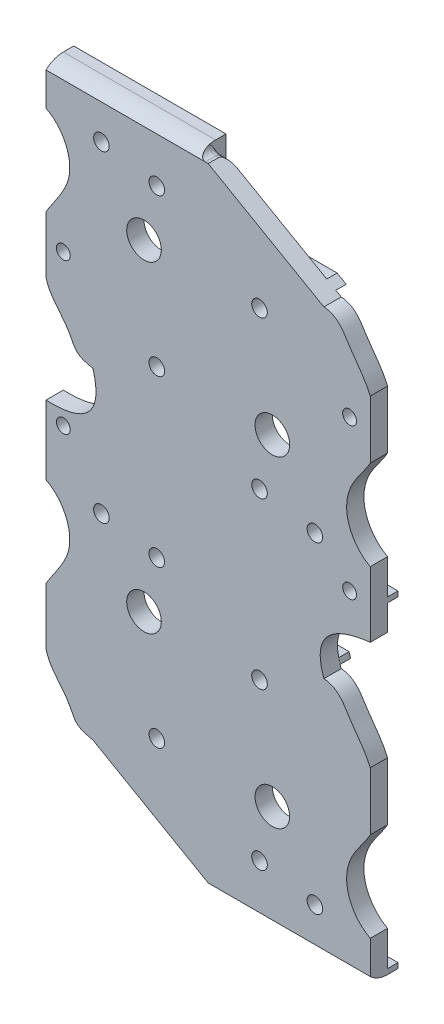
SolidWorks part; units mm, degrees
ref_plane "Front Plane" through (0, 0, 0) normal (0, 0, 1) x (1, 0, 0)
ref_plane "Top Plane" through (0, 0, 0) normal (0, 1, 0) x (1, 0, 0)
ref_plane "Right Plane" through (0, 0, 0) normal (1, 0, 0) x (0, 0, -1)
sketch "Sketch1" plane through (0, 0, 0) normal (0, 0, 1) x (1, 0, 0)
  line L0 (-19.7692, 94.7302) -> (-48.0392, 94.7302) construction
  line L1 (-46.8389, 110) -> (46.8389, 110)
  line L2 (-46.8389, 110) -> (-46.8389, -70)
  line L3 (-46.8389, -70) -> (46.8389, -70)
  line L4 (46.8389, 110) -> (46.8389, -70)
  line L5 (-46.8389, 27.4128) -> (-46.8389, 58.1094)
  line L6 (-46.8389, 100.4217) -> (-46.8597, 74.4838)
  line L7 (46.8389, 13.6344) -> (46.8389, -17.7446)
  line L8 (46.8389, 106.6344) -> (46.8389, 75.2554)
  line L9 (46.8389, 32.5783) -> (46.8597, 58.5162)
  line L10 (46.8389, -60.4217) -> (46.8597, -34.4838)
  line L11 (-46.8389, -65.5872) -> (-46.8389, -34.8906)
  line L12 (-46.8389, 7.4217) -> (-46.8597, -18.5162)
  line L13 (-33.2661, -50.893) -> (0, -70)
  line L14 (0, -70) -> (-46.8389, -70)
  line L15 (-46.8389, -34.8906) -> (-46.8389, -70)
  line L16 (33.4436, 90.8587) -> (0, 110)
  arc A0 (-42.3622, 81.2908) -> (-46.8389, 100.4217) centre (-53.2184, 88.8396) ccw construction
  arc A1 (-42.3622, 81.2908) -> (-46.8597, 74.4838) centre (98.8539, -16.903) ccw construction
  arc A2 (-44.9811, 54.2562) -> (-41.0297, 48.7592) centre (4.5296, 85.6771) ccw construction
  arc A3 (-38.5976, 44.9453) -> (-41.0297, 48.7592) centre (-56.5685, 36.1677) ccw construction
  arc A4 (-40.9236, 48.3818) -> (-37.2194, 45.4511) centre (-33.0423, 54.5369) ccw construction
  arc A5 (-38.5976, 44.9453) -> (-36.9529, 43.1656) centre (-34.8111, 46.7947) ccw construction
  arc A6 (-36.9529, 43.1656) -> (-29.4469, 41.75) centre (-29.4469, 62.3575) ccw construction
  circle A7 centre (-14.8389, 51.75) radius 2.25
  arc A8 (42.3622, 51.7092) -> (46.8389, 32.5783) centre (53.2184, 44.1604) ccw construction
  arc A9 (42.3622, 51.7092) -> (46.8597, 58.5162) centre (-98.8539, 149.903) ccw construction
  arc A10 (36.9529, 89.8344) -> (29.4469, 91.25) centre (29.4469, 70.6425) ccw construction
  circle A11 centre (-14.8389, 97) radius 2.25
  circle A12 centre (-30.8389, 100) radius 2.25
  circle A13 centre (14.8389, 81.25) radius 2.25
  circle A14 centre (14.8389, 36) radius 2.25
  circle A15 centre (30.8389, 33) radius 2.25
  circle A16 centre (-14.8389, -41.25) radius 2.25
  circle A17 centre (-14.8389, 4) radius 2.25
  circle A18 centre (-30.8389, 7) radius 2.25
  circle A19 centre (14.8389, -11.75) radius 2.25
  circle A20 centre (14.8389, -57) radius 2.25
  circle A21 centre (30.8389, -60) radius 2.25
  spline S0 degree 3 poles (-46.8389, 100.4217) (-42.2264, 98.1412) (-36.7036, 86.8939) (-44.5501, 78.531) (-46.8597, 74.4838) knots 0 0 0 0 0.513387 1 1 1 1
  spline S1 degree 3 poles (-46.8389, 58.1094) (-45.7586, 53.6552) (-40.8859, 50.4065) (-38.2385, 43.1366) (-34.7821, 42.4316) (-33.2661, 42.107) knots 0 0 0 0 0.587735 0.769686 1 1 1 1
  spline S2 degree 2 poles (-33.2661, 42.107) (-28.8924, 26.7095) (-46.8389, 27.4128) knots 0 0 0 1 1 1
  spline S3 degree 3 poles (46.8389, 32.5783) (42.9828, 34.6042) (38.9062, 41.1287) (41.1418, 51.3815) (45.2094, 55.5599) (46.8597, 58.5162) knots 0 0 0 0 0.434931 0.661678 1 1 1 1
  spline S4 degree 3 poles (46.8389, 75.2554) (45.396, 78.7223) (40.759, 83.9953) (37.5733, 90.552) (33.4436, 90.8587) knots 0 0 0 0 0.525455 1 1 1 1
  spline S7 degree 3 poles (-46.8389, -34.8906) (-45.7586, -39.3448) (-40.8859, -42.5935) (-38.2385, -49.8634) (-34.7821, -50.5684) (-33.2661, -50.893) knots 0 0 0 0 0.587735 0.769686 1 1 1 1
  spline S8 degree 3 poles (-46.8389, 7.4217) (-42.2264, 5.1412) (-36.7036, -6.1061) (-44.5501, -14.469) (-46.8597, -18.5162) knots 0 0 0 0 0.513387 1 1 1 1
  spline S9 degree 2 poles (33.4436, -2.1413) (28.4165, 11.5595) (46.8389, 13.6344) knots 0 0 0 1 1 1
  spline S10 degree 3 poles (46.8389, -17.7446) (45.396, -14.2777) (40.759, -9.0047) (37.5733, -2.448) (33.4436, -2.1413) knots 0 0 0 0 0.525455 1 1 1 1
  spline S11 degree 3 poles (46.8389, -60.4217) (42.9828, -58.3958) (38.9062, -51.8713) (41.1418, -41.6185) (45.2094, -37.4401) (46.8597, -34.4838) knots 0 0 0 0 0.434931 0.661678 1 1 1 1
  dimension "D1" = 4.5
  dimension "D2" = 4.5
  dimension "D3" = 4.5
  dimension "D4" = 4.5
  dimension "D6" = 44.75
  dimension "D5" = 2
extrude "Boss-Extrude1" add sketch "Sketch1" along normal blind 5 contours L4 S11 S10 S9 S3 S4 L1 L2 S0 S1 S2 S8 S7 L3 region at (-0.0047, 20.0102, 0)
sketch "Sketch2" plane through (0, 0, 0) normal (0, 0, -1) x (-1, 0, 0)
  line L1 (46.8389, 27.4128) -> (46.8389, 7.4217) construction
  line L3 (2.8389, 19) -> (46.8389, 19)
  line L4 (46.8389, 19) -> (46.8389, 17.5)
  line L5 (4.8389, 17) -> (46.8389, 17) construction
  line L6 (46.8389, 17.5) -> (4.3389, 17.5)
  line L7 (4.3389, 17.5) -> (4.3389, -51.75)
  line L8 (4.3389, -51.75) -> (31.774, -51.75)
  line L9 (33.2661, -50.893) -> (0, -70) construction
  line L10 (31.774, -51.75) -> (29.1624, -53.25)
  line L11 (29.1624, -53.25) -> (2.8389, -53.25)
  line L12 (2.8389, -53.25) -> (2.8389, 19)
  line L14 (4.8389, 17) -> (4.8389, -51.25) construction
  line L15 (-33.1375, -1.25) -> (-32.7243, 0.25)
  line L16 (4.8389, -51.25) -> (29.4469, -51.25) construction
  line L17 (46.8389, 110.5) -> (4.3389, 110.5)
  line L18 (46.8389, 112) -> (46.8389, 110.5)
  line L19 (2.8389, 112) -> (46.8389, 112)
  line L20 (2.8389, 39.75) -> (2.8389, 112)
  line L21 (4.3389, 110.5) -> (4.3389, 41.25)
  line L22 (32.7098, 39.75) -> (2.8389, 39.75)
  line L23 (4.3389, 41.25) -> (33.0368, 41.25)
  line L25 (-46.8389, -60.4217) -> (-46.8389, -70) construction
  line L26 (33.0368, 41.25) -> (32.7098, 39.75)
  line L27 (-2.8389, 21) -> (-46.8389, 21)
  line L28 (4.8389, 41.75) -> (29.4469, 41.75) construction
  line L29 (46.8389, 110) -> (0, 110) construction
  line L30 (4.8389, 110) -> (4.8389, 41.75) construction
  line L31 (46.8389, 110) -> (46.8389, 100.4217) construction
  line L32 (-46.8389, 22.5) -> (-4.3389, 22.5)
  line L33 (-46.8389, 21) -> (-46.8389, 22.5)
  line L34 (-2.8389, 93.25) -> (-2.8389, 21)
  line L35 (-4.3389, 22.5) -> (-4.3389, 91.75)
  line L36 (-29.2656, 93.25) -> (-2.8389, 93.25)
  line L37 (-4.3389, 91.75) -> (-31.8864, 91.75)
  line L39 (-4.8389, 23) -> (-46.8389, 23) construction
  line L40 (-33.4436, 90.8587) -> (0, 110) construction
  line L41 (-29.2656, 93.25) -> (-31.8864, 91.75)
  line L42 (-4.8389, 91.25) -> (-29.4469, 91.25) construction
  line L43 (-4.8389, 23) -> (-4.8389, 91.25) construction
  line L44 (-46.8389, -70.5) -> (-4.3389, -70.5)
  line L45 (-4.3389, -70.5) -> (-4.3389, -1.25)
  line L46 (-4.3389, -1.25) -> (-33.1375, -1.25)
  line L47 (-32.7243, 0.25) -> (-2.8389, 0.25)
  line L48 (-2.8389, 0.25) -> (-2.8389, -72)
  line L49 (-2.8389, -72) -> (-46.8389, -72)
  line L50 (-46.8389, -72) -> (-46.8389, -70.5)
  line L51 (0, -70) -> (-46.8389, -70) construction
  line L52 (-4.8389, -70) -> (-4.8389, -1.75) construction
  line L53 (-4.8389, -1.75) -> (-29.4469, -1.75) construction
  line L54 (-46.8389, 32.5783) -> (-46.8389, 13.6344) construction
  parabola Q0 (33.2661, 42.107) -> (46.8389, 27.4128) focus (36.8258, 33.5048) apex (33.9207, 31.4092) construction
  parabola Q1 (33.2661, 42.107) -> (46.8389, 27.4128) focus (36.8258, 33.5048) apex (33.9207, 31.4092) construction
  parabola Q2 (33.2661, 42.107) -> (46.8389, 27.4128) focus (36.8258, 33.5048) apex (33.9207, 31.4092) construction
  parabola Q5 (-33.4436, -2.1413) -> (-46.8389, 13.6344) focus (-36.6663, 5.3308) apex (-33.2144, 7.0422) construction
  parabola Q6 (-33.4436, -2.1413) -> (-46.8389, 13.6344) focus (-36.6663, 5.3308) apex (-33.2144, 7.0422) construction
  dimension "D1" = 0.5
  dimension "D2" = 1.5
  dimension "D3" = 1.5
  dimension "D4" = 0.5
  dimension "D5" = 1.5
  dimension "D6" = 0.5
  dimension "D8" = 1.5
  dimension "D7" = 0.5
  dimension "D9" = 1.5
  dimension "D10" = 0.5
  dimension "D11" = 0.5
  dimension "D12" = 1.5
  dimension "D13" = 0.5
  dimension "D14" = 1.5
  dimension "D15" = 1.5
  dimension "D16" = 0.5
  dimension "D17" = 0.5
  dimension "D18" = 1.5
  dimension "D20" = 0.5
  dimension "D19" = 0.5
  dimension "D21" = 1.5
  dimension "D22" = 0.5
  dimension "D23" = 1.5
  dimension "D24" = 1.5
extrude "Boss-Extrude2" add sketch "Sketch2" along normal blind 3
sketch "Sketch4" plane through (-46.8389, 0, 0) normal (-1, 0, 0) x (0, 0, 1)
  line L0 (-3, 112) -> (0, 112) construction
  line L1 (0, 112) -> (0, 110)
  line L2 (0, 110) -> (5, 110)
  arc A0 (0, 112) -> (5, 110) centre (0, 104.75) cw
extrude "Boss-Extrude3" add sketch "Sketch4" against normal up to surface (44 mm away) up to face at (-2.8389, 82.7, -1.2)
sketch "Sketch5" plane through (46.8389, 0, 0) normal (1, 0, 0) x (0, 0, -1)
  line L0 (3, -72) -> (0, -72) construction
  line L1 (-5, -70) -> (0, -70)
  line L2 (0, -70) -> (0, -72)
  arc A0 (0, -72) -> (-5, -70) centre (0, -64.75) cw
extrude "Boss-Extrude4" add sketch "Sketch5" against normal up to surface (44 mm away) up to face at (2.8389, -42.7, -1.2)
fillet "Fillet1" radius 2 1 edges at (2.8389, -70, 2.5)
fillet "Fillet2" radius 2 2 edges at (0.4194, -70, 0) (2.2531, -70.5858, 0)
fillet "Fillet3" radius 2 1 edges at (-2.8389, 110, 2.5)
fillet "Fillet4" radius 2 2 edges at (-0.4194, 110, 0) (-2.2531, 110.5858, 0)
sketch "Sketch7" plane through (0, 0, 5) normal (0, 0, 1) x (1, 0, 0)
  circle A0 centre (-41.8389, 23.5) radius 2
  circle A1 centre (-41.8389, 67) radius 2
  circle A2 centre (40.8611, 67) radius 2
  circle A3 centre (40.8611, 23.5) radius 2
  dimension "D1" = 4
  dimension "D2" = 4
  dimension "D3" = 4
  dimension "D4" = 4
extrude "Cut-Extrude1" cut sketch "Sketch7" against normal blind 10
sketch "Sketch8" plane through (0, 0, 0) normal (0, 0, -1) x (-1, 0, 0)
  circle A0 centre (-18.5389, -41.6) radius 5
  circle A1 centre (-18.5389, 51.4) radius 5
  circle A2 centre (18.5389, 81.6) radius 5
  circle A3 centre (18.5389, -11.4) radius 5
  dimension "D1" = 10
extrude "Cut-Extrude2" cut sketch "Sketch8" against normal blind 10
